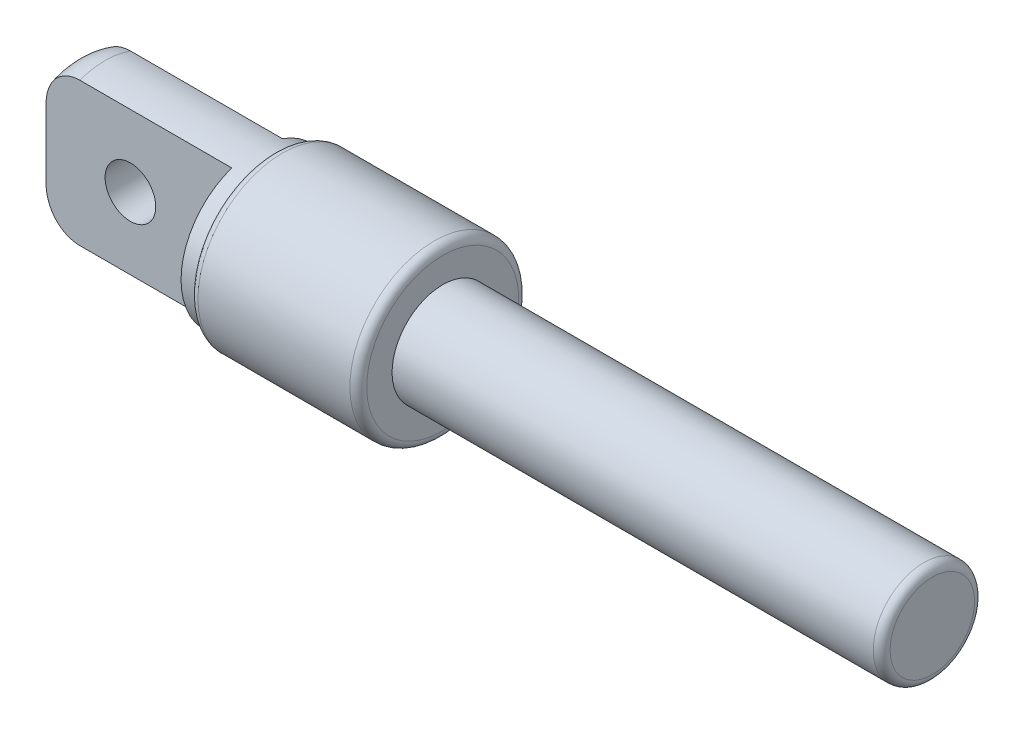
SolidWorks part; units mm, degrees
ref_plane "前视基准面" through (0, 0, 0) normal (0, 0, 1) x (1, 0, 0)
ref_plane "上视基准面" through (0, 0, 0) normal (0, 1, 0) x (1, 0, 0)
ref_plane "右视基准面" through (0, 0, 0) normal (1, 0, 0) x (0, 0, -1)
sketch "草图1" plane through (0, 0, 0) normal (0, 0, 1) x (1, 0, 0)
  line L0 (0, 0) -> (-9, 0) construction
  line L1 (0, 0) -> (0, 3)
  line L2 (0, 3) -> (-29, 3)
  line L3 (-29, 3) -> (-29, 5)
  line L4 (-29, 5) -> (-39, 5)
  line L5 (-39, 5) -> (-39, 4.5)
  line L6 (-39, 4.5) -> (-51, 4.5)
  line L7 (-51, 4.5) -> (-51, 0)
  line L8 (-51, 0) -> (0, 0)
  dimension "D1" = 6
  dimension "D2" = 10
  dimension "D3" = 9
  dimension "D4" = 29
  dimension "D5" = 10
  dimension "D6" = 51
revolve "旋转1" add sketch "草图1" angle 360 about L0
fillet "圆角1" radius 2 1 edges at (-51, 4.5, 0)
sketch "草图2" plane through (-51, 0, 0) normal (-1, 0, 0) x (0, 0, 1)
  line L1 (-1.5, 5.8028) -> (1.5, 5.8028)
  line L2 (-1.5, 5.8028) -> (-1.5, -6.1588)
  line L3 (-1.5, -6.1588) -> (1.5, -6.1588)
  line L4 (1.5, 5.8028) -> (1.5, -6.1588)
  circle A0 centre (0, 0) radius 7.3214
  point P4 (0, 5.8028)
  dimension "D1" = 3
extrude "切除-拉伸1" cut sketch "草图2" against normal blind 11
sketch "草图3" plane through (0, 0, -1.5) normal (0, 0, -1) x (-1, 0, 0)
  line L0 (51, 2) -> (51, -2) construction
  circle A0 centre (46, 0) radius 1.5
  point P4 (51, 0)
  dimension "D1" = 3
  dimension "D2" = 5
extrude "切除-拉伸2" cut sketch "草图3" against normal up to surface (3 mm away) up to face at (-46.7581, -0.066, 1.5)
fillet "圆角2" radius 0.5 3 edges at (-29, 5, 0) (-39, 5, 0) (0, 3, 0)
